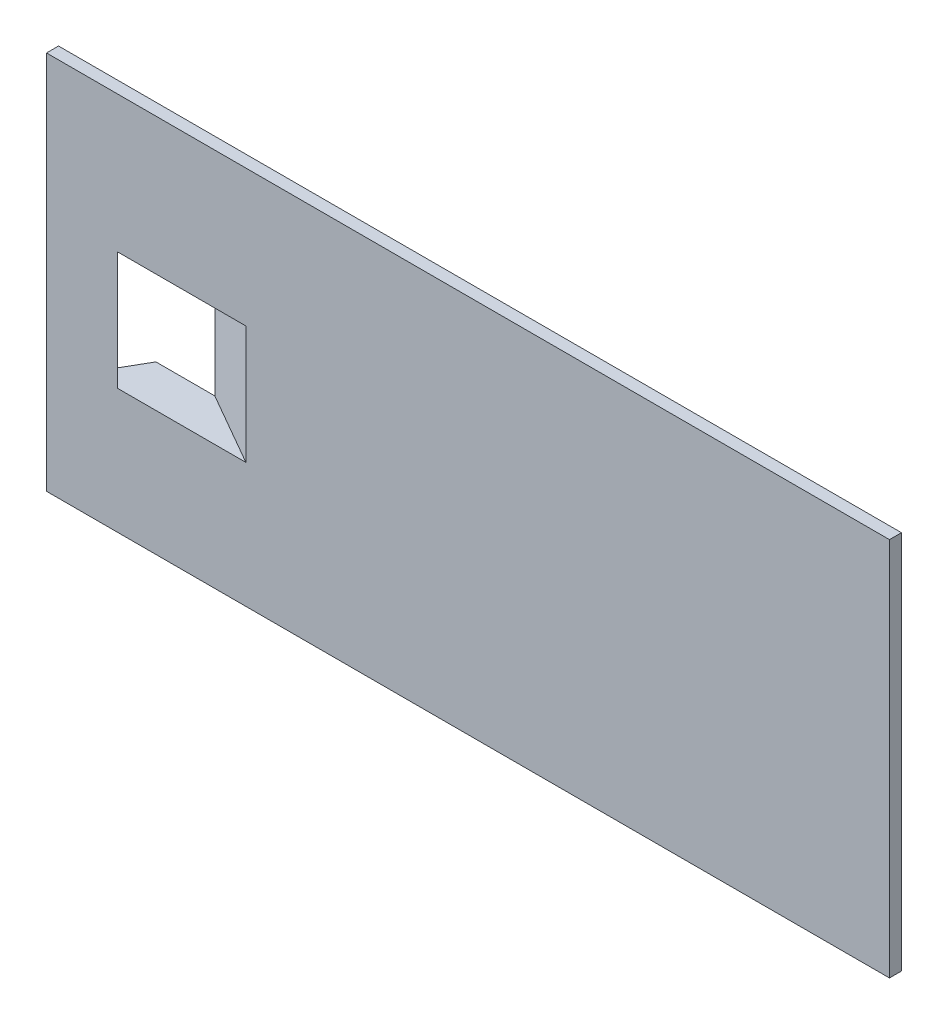
SolidWorks part; units mm, degrees
ref_plane "Front Plane" through (0, 0, 0) normal (0, 0, 1) x (1, 0, 0)
ref_plane "Top Plane" through (0, 0, 0) normal (0, 1, 0) x (1, 0, 0)
ref_plane "Right Plane" through (0, 0, 0) normal (1, 0, 0) x (0, 0, -1)
sketch "Sketch1" plane through (0, 0, 0) normal (0, 0, 1) x (1, 0, 0)
  line L1 (-126.4938, -45.2831) -> (2.5697, -45.2831)
  line L2 (-126.4938, -45.2831) -> (-126.4938, 12.5794)
  line L3 (-126.4938, 12.5794) -> (2.5697, 12.5794)
  line L4 (2.5697, -45.2831) -> (2.5697, 12.5794)
  line L5 (-126.4938, -45.2831) -> (2.5697, 12.5794) construction
  line L6 (-126.4938, 12.5794) -> (2.5697, -45.2831) construction
  point P0 (-61.9621, -16.3519)
  point P5 (2.5697, -48.5767)
extrude "Boss-Extrude1" add sketch "Sketch1" along normal blind 5
sketch "Sketch2" plane through (0, 0, 0) normal (0, 0, -1) x (-1, 0, 0)
  line L1 (50.5486, -38.5474) -> (14.2877, -38.5474)
  line L2 (50.5486, -38.5474) -> (50.5486, 6.6921)
  line L3 (50.5486, 6.6921) -> (14.2877, 6.6921)
  line L4 (14.2877, -38.5474) -> (14.2877, 6.6921)
  line L5 (50.5486, -38.5474) -> (14.2877, 6.6921) construction
  line L6 (50.5486, 6.6921) -> (14.2877, -38.5474) construction
  line L7 (49.8095, -37.7028) -> (15.0267, -37.7028)
  line L8 (49.8095, -37.7028) -> (49.8095, 5.8475)
  line L9 (49.8095, 5.8475) -> (15.0267, 5.8475)
  line L10 (15.0267, -37.7028) -> (15.0267, 5.8475)
  line L11 (49.8095, -37.7028) -> (15.0267, 5.8475) construction
  line L12 (49.8095, 5.8475) -> (15.0267, -37.7028) construction
  point P0 (32.4181, -15.9276)
  point P5 (29.0156, -12.5739)
  point P6 (32.4181, -15.9276)
  point P11 (31.5127, -12.7779)
  point P12 (31.8702, -14.0102)
  point P13 (32.3017, -17.6957)
  point P14 (32.6138, -14.9651)
  point P15 (32.4181, -15.9276)
extrude "Boss-Extrude2" add sketch "Sketch2" along normal blind 1
sketch "Sketch3" plane through (0, 0, 0) normal (0, 0, -1) x (-1, 0, 0)
  circle A0 centre (5.8472, -15.8094) radius 3.5601
  point P2 (0, 0)
extrude "Boss-Extrude3" add sketch "Sketch3" along normal blind 1
sketch "Sketch4" plane through (0, 0, -1) normal (0, 0, -1) x (-1, 0, 0)
  line L0 (7.4982, -13.5037) -> (7.4299, -14.2268)
  line L1 (7.3138, -18.3414) -> (7.3192, -17.6008)
  arc A0 (7.4982, -13.5037) -> (7.3138, -18.3414) centre (5.955, -15.8672) ccw
  arc A1 (7.4299, -14.2268) -> (7.3192, -17.6008) centre (5.955, -15.8672) ccw
  point P1 (0, 0)
extrude "Cut-Extrude2" cut sketch "Sketch4" against normal blind 0.5
sketch "Sketch5" plane through (0, 0, -1) normal (0, 0, -1) x (-1, 0, 0)
  line L0 (8.3401, -15.4929) -> (5.464, -15.4382)
  line L1 (8.3401, -16.1787) -> (5.464, -16.2334)
  arc A0 (8.3401, -16.1787) -> (8.3401, -15.4929) centre (8.3401, -15.8358) ccw
  arc A1 (5.464, -15.4382) -> (5.464, -16.2334) centre (5.464, -15.8358) ccw
extrude "Cut-Extrude3" cut sketch "Sketch5" against normal blind 0.5
sketch "Sketch11" plane through (0, 0, 5) normal (0, 0, 1) x (1, 0, 0)
  line L1 (-134.7361, -48.3572) -> (5.5329, -48.3572)
  line L2 (-134.7361, -48.3572) -> (-134.7361, 14.8126)
  line L3 (-134.7361, 14.8126) -> (5.5329, 14.8126)
  line L4 (5.5329, -48.3572) -> (5.5329, 14.8126)
  line L5 (-134.7361, -48.3572) -> (5.5329, 14.8126) construction
  line L6 (-134.7361, 14.8126) -> (5.5329, -48.3572) construction
  point P0 (-64.6016, -16.7723)
extrude "Boss-Extrude4" add sketch "Sketch11" along normal blind 2
sketch "Sketch12" plane through (2.5697, 0, 0) normal (1, 0, 0) x (0, 0, -1)
  line L0 (-5.0495, 12.5555) -> (1.3768, 8.6378)
  line L1 (1.3768, 8.6378) -> (1.4949, 17.885)
  line L2 (1.4949, 17.885) -> (-5.0495, 12.5555)
  point P0 (-5.0495, 12.5555)
extrude "Cut-Extrude11" cut sketch "Sketch12" against normal through all
sketch "Sketch13" plane through (0, 14.8126, 0) normal (0, 1, 0) x (1, 0, 0)
  line L0 (-126.4051, -5) -> (-129.311, 1.469)
  line L1 (5.5329, -5) -> (-134.7361, -5) construction
  line L2 (-129.311, 1.469) -> (-122.3741, 2.0143)
  line L3 (-122.3741, 2.0143) -> (-126.4051, -5)
extrude "Cut-Extrude12" cut sketch "Sketch13" against normal through all
sketch "Sketch14" plane through (-134.7361, 0, 0) normal (-1, 0, 0) x (0, 0, 1)
  line L0 (5, -45.2349) -> (-1.3308, -41.1782)
  line L1 (5, 12.5253) -> (5, -48.3572) construction
  line L2 (-1.3308, -41.1782) -> (-1.6233, -49.506)
  line L3 (-1.6233, -49.506) -> (5, -45.2349)
  point P4 (5, -45.2349)
extrude "Cut-Extrude15" cut sketch "Sketch14" against normal through all
sketch "Sketch15" plane through (0, -48.3572, 0) normal (0, -1, 0) x (-1, 0, 0)
  line L0 (-2.5596, -5) -> (1.7788, 1.2395)
  line L1 (134.7361, -5) -> (-5.5329, -5) construction
  line L2 (1.7788, 1.2395) -> (-4.0713, 1.1275)
  line L3 (-4.0713, 1.1275) -> (-2.5596, -5)
  point P4 (-2.5263, -5)
  point P8 (-2.5596, -5)
extrude "Cut-Extrude18" cut sketch "Sketch15" against normal through all
sketch "Sketch17" plane through (-92.8622, 0, -53.367) normal (-0.867, 0, -0.4983) x (-0.4983, 0, 0.867)
  line L0 (67.3189, -45.2349) -> (67.3189, 12.5253) construction
  line L1 (76.0148, -27.6038) -> (56.6698, -27.6038)
  line L2 (76.0148, -27.6038) -> (76.0148, -7.9428)
  line L3 (76.0148, -7.9428) -> (56.6698, -7.9428)
  line L4 (56.6698, -27.6038) -> (56.6698, -7.9428)
  line L5 (76.0148, -27.6038) -> (56.6698, -7.9428) construction
  line L6 (76.0148, -7.9428) -> (56.6698, -27.6038) construction
  line L9 (66.9474, -18.8095) -> (67.3189, -18.8095)
  point P0 (66.3423, -17.7733)
  point P5 (66.3423, -17.7733)
  point P7 (66.3423, -17.7733)
  line M2 (61.552, 9.4772) -> (61.552, -42.031)
  line M4 (67.3189, -45.2349) -> (67.3189, 12.5253)
extrude "Cut-Extrude20" cut sketch "Sketch17" against normal blind 40 contours L3 L1 M4 M2 | L4 L1 L3 M2 region at (-124.9684, -17.7733, 2.5) region at (-122.3153, -17.7733, -2.1165)
